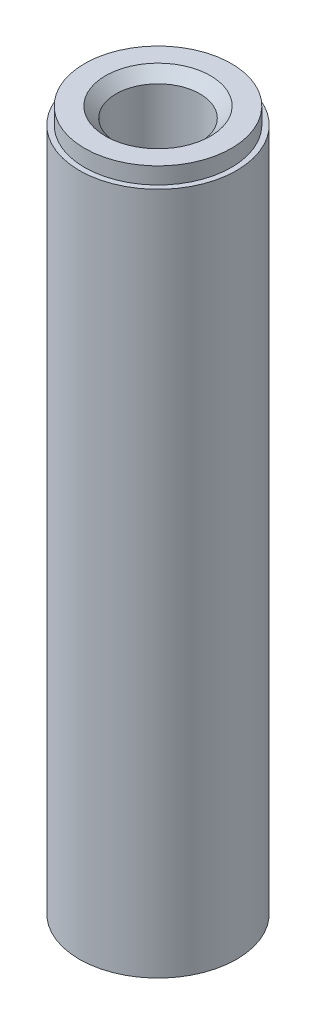
SolidWorks part; units mm, degrees
material "Natural Rubber"
ref_plane "Front Plane" through (0, 0, 0) normal (0, 0, 1) x (1, 0, 0)
ref_plane "Top Plane" through (0, 0, 0) normal (0, 1, 0) x (1, 0, 0)
ref_plane "Right Plane" through (0, 0, 0) normal (1, 0, 0) x (0, 0, -1)
sketch "Sketch1" plane through (0, 0, 0) normal (0, 1, 0) x (1, 0, 0)
  circle A0 centre (0, 0) radius 37.5
  circle A1 centre (0, 0) radius 20
  dimension "D1" = 75
  dimension "D2" = 40
extrude "Boss-Extrude1" add sketch "Sketch1" along normal blind 333.5
sketch "Sketch2" plane through (0, 333.5, 0) normal (0, 1, 0) x (1, 0, 0)
  circle A0 centre (0, 0) radius 35
  circle A1 centre (0, 0) radius 57.2901
  dimension "D1" = 70
extrude "Cut-Extrude1" cut sketch "Sketch2" against normal blind 7.9
chamfer "Chamfer2" distance 5 angle 45 1 edges at (0, 333.5, 20)
